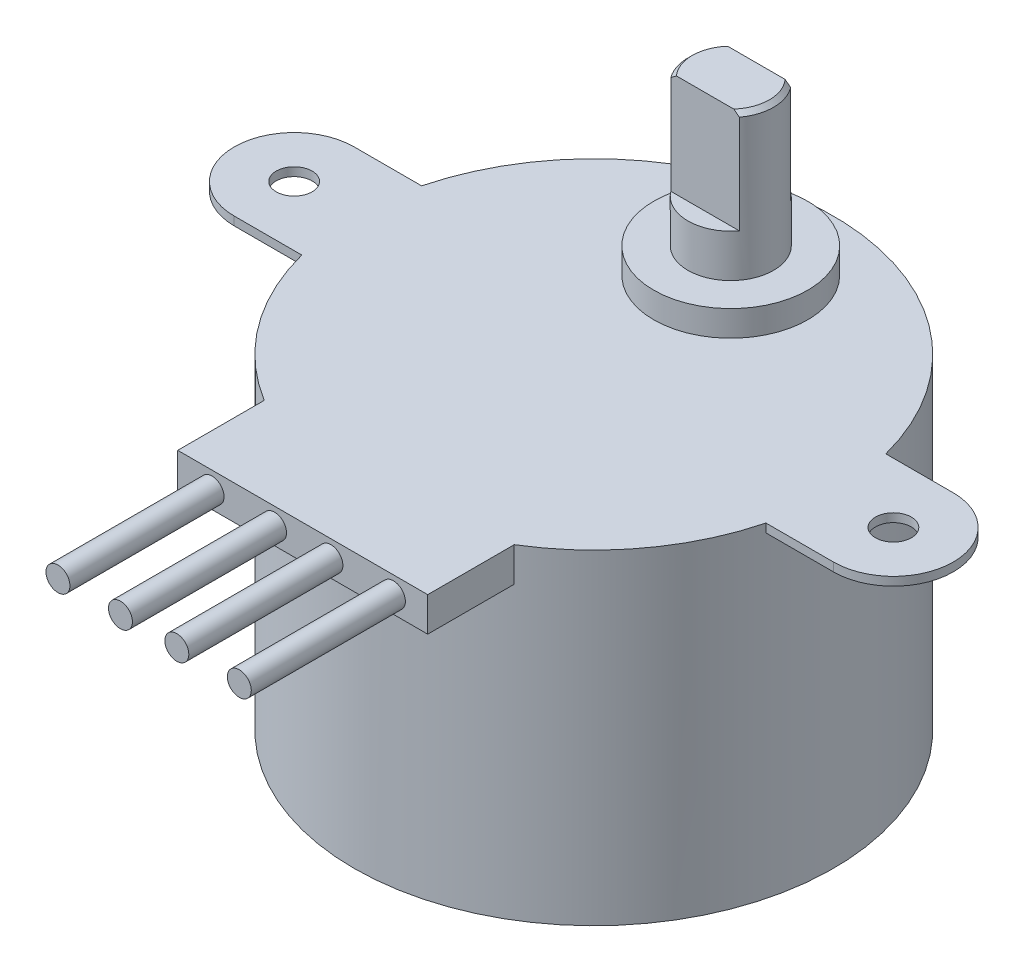
SolidWorks part; units mm, degrees
ref_plane "Front Plane" through (0, 0, 0) normal (0, 0, 1) x (1, 0, 0)
ref_plane "Top Plane" through (0, 0, 0) normal (0, 1, 0) x (1, 0, 0)
ref_plane "Right Plane" through (0, 0, 0) normal (1, 0, 0) x (0, 0, -1)
sketch "Sketch1" plane through (0, 0, 0) normal (0, 1, 0) x (1, 0, 0)
  circle A0 centre (0, 0) radius 14
  dimension "D1" = 28
extrude "Boss-Extrude1" add sketch "Sketch1" along normal blind 19
sketch "Sketch2" plane through (0, 19, 0) normal (0, 1, 0) x (1, 0, 0)
  line L0 (0, 0) -> (0, 8)
  circle A0 centre (0, 8) radius 4.5
  dimension "D1" = 8
extrude "Boss-Extrude2" add sketch "Sketch2" along normal blind 1.5 contours A0
sketch "Sketch3" plane through (0, 20.5, 0) normal (0, 1, 0) x (1, 0, 0)
  circle A0 centre (0, 8) radius 2.5
extrude "Boss-Extrude3" add sketch "Sketch3" along normal blind 2.5
sketch "Sketch4" plane through (0, 23, 0) normal (0, 1, 0) x (1, 0, 0)
  circle A0 centre (0, 8) radius 2.5
  dimension "D1" = 5
extrude "Boss-Extrude4" add sketch "Sketch4" along normal blind 6
chamfer "Chamfer1" distance 0.25 1 edges at (0, 29, -5.5)
sketch "Sketch6" plane through (0, 19, 0) normal (0, 1, 0) x (1, 0, 0)
  line L0 (0, 0) -> (0, 3.5) construction
  line L1 (0, 0) -> (14, 0) construction
  line L2 (-17.5, 3.5) -> (17.5, 3.5)
  line L3 (17.5, -3.5) -> (-17.5, -3.5)
  line L4 (14, 0) -> (16.45, 0) construction
  line L5 (16.45, 0) -> (17.5, 0)
  circle A0 centre (17.5, 0) radius 1.05
  arc A1 (17.5, -3.5) -> (17.5, 3.5) centre (17.5, 0) ccw
  arc A2 (17.5, 3.5) -> (14, 0) centre (17.5, 0) ccw construction
  arc A3 (14, 0) -> (17.5, -3.5) centre (17.5, 0) ccw construction
  circle A4 centre (-17.5, 0) radius 1.05
  arc A5 (-17.5, -3.5) -> (-17.5, 3.5) centre (-17.5, 0) cw
  point P13 (0, -3.5)
  circle M9 centre (0, 0) radius 14
  dimension "D3" = 2.1
  dimension "D1" = 3.5
  dimension "D2" = 17.5
extrude "Boss-Extrude5" add sketch "Sketch6" against normal blind 0.5 contours A5 L3 L2 A4 M9 | L3 A1 L2 A0 M9 region at (-15.5277, 19, -3.3978) region at (15.5277, 19, -3.3978)
sketch "Sketch7" plane through (0, 29, 0) normal (0, 1, 0) x (1, 0, 0)
  line L0 (0, 8) -> (0, 9.5) construction
  line L1 (0, 8) -> (0, 6.5) construction
  line L2 (0, 9.5) -> (-3.8527, 9.5)
  line L3 (-3.8527, 9.5) -> (-3.8527, 12.8083)
  line L4 (-3.8527, 12.8083) -> (3.6924, 12.8083)
  line L5 (3.6924, 12.8083) -> (3.6924, 9.5)
  line L6 (3.6924, 9.5) -> (0, 9.5)
  line L7 (0, 8) -> (3.0228, 8) construction
  line L8 (3.6924, 6.5) -> (0, 6.5)
  line L9 (3.6924, 3.1917) -> (3.6924, 6.5)
  line L10 (-3.8527, 3.1917) -> (3.6924, 3.1917)
  line L11 (-3.8527, 6.5) -> (-3.8527, 3.1917)
  line L12 (0, 6.5) -> (-3.8527, 6.5)
  dimension "D1" = 1.5
extrude "Cut-Extrude1" cut sketch "Sketch7" against normal blind 6
sketch "Sketch8" plane through (0, 19, 0) normal (0, 1, 0) x (1, 0, 0)
  line L0 (7.3, -17) -> (-7.3, -17)
  line L1 (7.3, 0) -> (7.3, -17)
  line L2 (-7.3, 0) -> (7.3, 0)
  line L3 (0, 0) -> (0, -7.0426) construction
  line L4 (-7.3, 0) -> (-7.3, -17)
  point P7 (0, -17)
  dimension "D1" = 17
  dimension "D2" = 7.3
extrude "Boss-Extrude6" add sketch "Sketch8" against normal blind 2
sketch "Sketch9" plane through (0, 0, 17) normal (0, 0, 1) x (1, 0, 0)
  line L0 (0, 19) -> (0, 17)
  line L1 (-7.3, 19) -> (7.3, 19) construction
  line L2 (-7.3, 17) -> (7.3, 17) construction
  line L6 (-3.2917, 19) -> (-7.3, 17) construction
  line L7 (-3.2917, 19) -> (0, 17) construction
  circle A2 centre (-5.2958, 18) radius 0.7
  circle A3 centre (-1.6458, 18) radius 0.7
  circle A4 centre (1.6458, 18) radius 0.7
  circle A5 centre (5.2958, 18) radius 0.7
extrude "Boss-Extrude7" add sketch "Sketch9" along normal blind 9 contours A3 | A4 | A5 | A2 region at (-1.6458, 18, 17) region at (1.6458, 18, 17) region at (5.2958, 18, 17)
